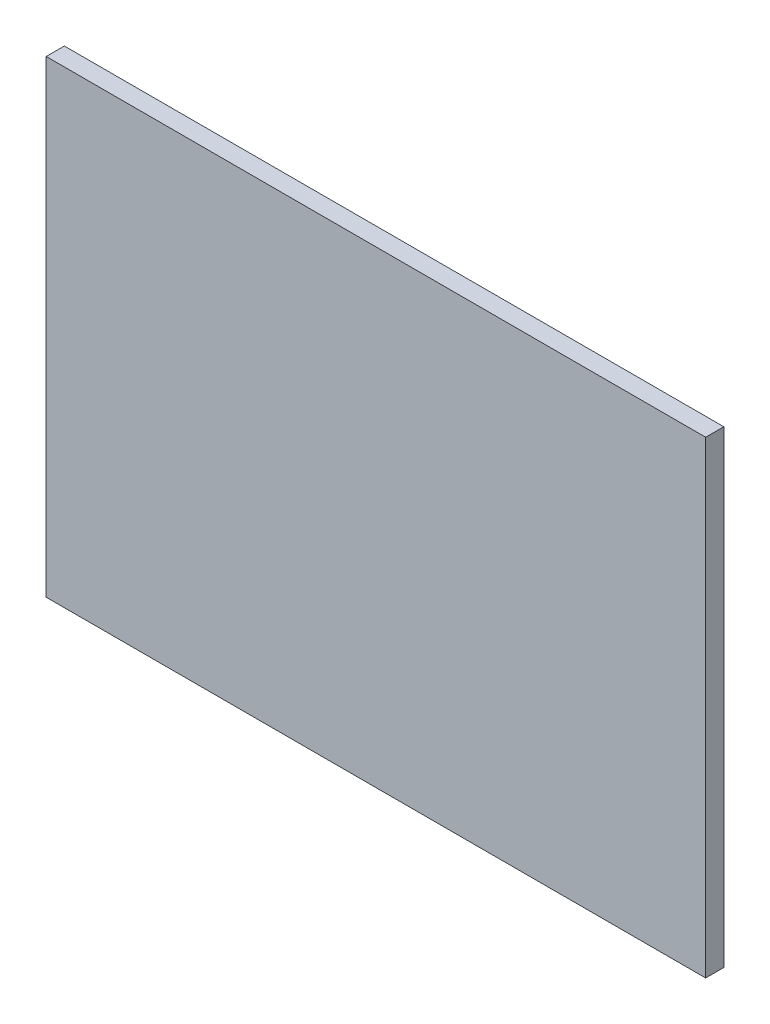
SolidWorks part; units mm, degrees
ref_plane "Front Plane" through (0, 0, 0) normal (0, 0, 1) x (1, 0, 0)
ref_plane "Top Plane" through (0, 0, 0) normal (0, 1, 0) x (1, 0, 0)
ref_plane "Right Plane" through (0, 0, 0) normal (1, 0, 0) x (0, 0, -1)
sketch "Sketch1" plane through (0, 0, 0) normal (0, 0, 1) x (1, 0, 0)
  line L1 (-31.1136, 31.4273) -> (37.8864, 31.4273)
  line L2 (-31.1136, 31.4273) -> (-31.1136, -17.5727)
  line L3 (-31.1136, -17.5727) -> (37.8864, -17.5727)
  line L4 (37.8864, 31.4273) -> (37.8864, -17.5727)
  dimension "D1" = 69
  dimension "D2" = 49
base flange "Base-Flange1" sketch "Sketch1" thickness 1.8974 reverse thickness direction no parameters "D1"=2.54
sketch "Bend-Lines1" plane through (0, 0, 0) normal (0, 1, 0) x (1, 0, 0)
sketch "Bounding-Box1" plane through (0, 0, 0) normal (0, 1, 0) x (1, 0, 0)
sheet metal parameters "Sheet-Metal1" thickness 1.8974 parameters "D1"=2.54
flat pattern "Flat-Pattern1" [suppressed]
sketch "Bend-Lines2" plane through (0, 0, 0) normal (0, 1, 0) x (1, 0, 0)
sketch "Bounding-Box2" [suppressed] plane through (0, 0, 0) normal (0, 1, 0) x (1, 0, 0)
